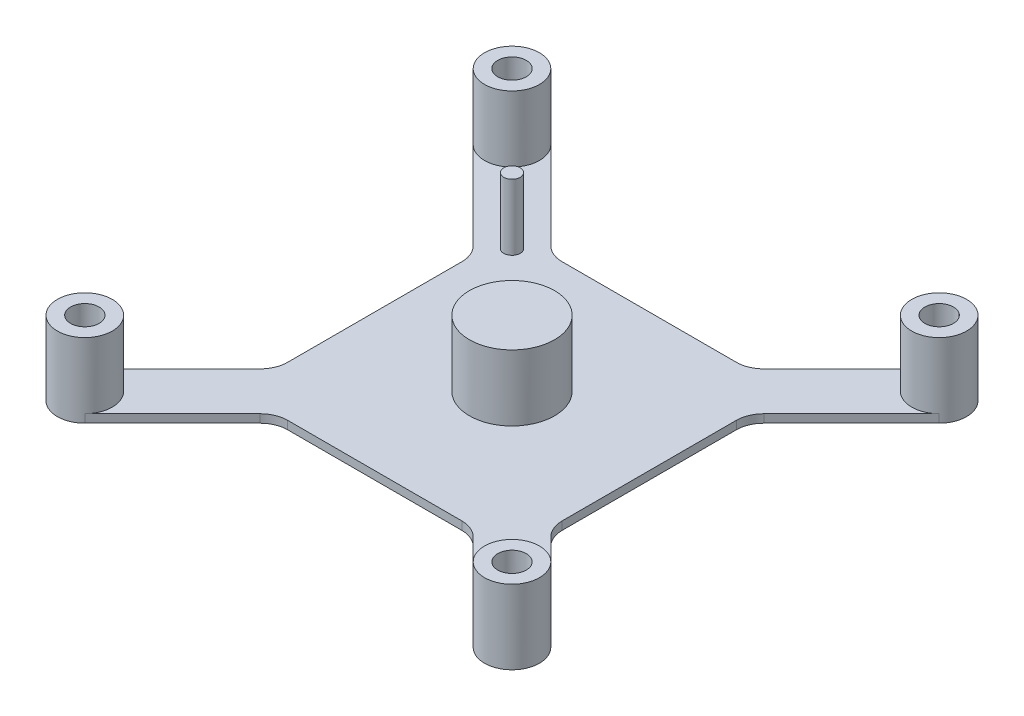
SolidWorks part; units mm, degrees
ref_plane "Front Plane" through (0, 0, 0) normal (0, 0, 1) x (1, 0, 0)
ref_plane "Top Plane" through (0, 0, 0) normal (0, 1, 0) x (1, 0, 0)
ref_plane "Right Plane" through (0, 0, 0) normal (1, 0, 0) x (0, 0, -1)
sketch "Sketch1" plane through (0, 0, 0) normal (0, 1, 0) x (1, 0, 0)
  line L1 (-25, -25) -> (25, -25)
  line L2 (-25, -25) -> (-25, 25)
  line L3 (-25, 25) -> (25, 25)
  line L4 (25, -25) -> (25, 25)
  line L5 (-25, -25) -> (25, 25) construction
  line L6 (-25, 25) -> (25, -25) construction
  circle A0 centre (0, 0) radius 8
  point P0 (0, 0)
  dimension "D2" = 16
  dimension "D1" = 50
extrude "Boss-Extrude1" add sketch "Sketch1" along normal blind 1.5
sketch "Sketch3" plane through (0, 1.5, 0) normal (0, 1, 0) x (1, 0, 0)
  line L0 (0, 0) -> (0, -6.5515) construction
  line L1 (-23, -25) -> (-15, -25)
  line L2 (-25, -23) -> (-25, -15)
  line L3 (-25, -15) -> (-17, -15)
  line L4 (-15, -25) -> (-15, -17)
  line L5 (0, -6.5515) -> (0, 0) construction
  line L6 (0, 0) -> (-7.2066, 0) construction
  line L7 (-25, 15) -> (-17, 15)
  line L8 (-15, 25) -> (-15, 17)
  line L9 (-23, 25) -> (-15, 25)
  line L10 (-25, 23) -> (-25, 15)
  line L11 (25, -15) -> (17, -15)
  line L12 (15, -25) -> (15, -17)
  line L13 (23, -25) -> (15, -25)
  line L14 (25, -23) -> (25, -15)
  line L15 (25, 23) -> (25, 15)
  line L16 (23, 25) -> (15, 25)
  line L17 (15, 25) -> (15, 17)
  line L18 (25, 15) -> (17, 15)
  line L19 (-25, 22.5) -> (-22.5, 22.5) construction
  line L20 (-22.5, 22.5) -> (-22.5, 25) construction
  arc A0 (23, -25) -> (25, -23) centre (23, -23) ccw
  arc A1 (25, 23) -> (23, 25) centre (23, 23) ccw
  arc A2 (-23, 25) -> (-25, 23) centre (-23, 23) ccw
  arc A3 (-23, -25) -> (-25, -23) centre (-23, -23) cw
  arc A4 (17, -15) -> (15, -17) centre (17, -17) ccw
  arc A5 (15, 17) -> (17, 15) centre (17, 17) ccw
  arc A6 (-17, 15) -> (-15, 17) centre (-17, 17) ccw
  arc A7 (-17, -15) -> (-15, -17) centre (-17, -17) cw
  circle A16 centre (-22.5, 22.5) radius 1.5
  circle A17 centre (-17, 17) radius 1.5
  point P23 (25, -25)
  point P26 (25, 25)
  point P29 (-25, 25)
  point P32 (-25, -25)
  point P35 (15, -15)
  point P38 (15, 15)
  point P41 (-15, 15)
  point P44 (-15, -15)
  dimension "D2" = 2
  dimension "D3" = 2.5
  dimension "D4" = 3
  dimension "D6" = 3
  dimension "D1" = 10
  dimension "D5" = 2.5
sketch "Sketch5" plane through (0, 1.5, 0) normal (0, 1, 0) x (1, 0, 0)
  line L0 (0, 0) -> (0, 33.3014) construction
  line L1 (0, 0) -> (36.9203, 0) construction
  line L2 (0, 0) -> (38.8909, 38.8909) construction
  line L3 (0, 0) -> (-38.8909, -38.8909) construction
  line L4 (-35.3553, -42.4264) -> (-42.4264, -35.3553) construction
  line L5 (42.4264, 35.3553) -> (35.3553, 42.4264) construction
  line L6 (-42.4264, -35.3553) -> (-25, -17.9289)
  line L7 (-25, 25) -> (-25, -25) construction
  line L8 (-35.3553, -42.4264) -> (-17.9289, -25)
  line L9 (-25, -25) -> (25, -25) construction
  line L10 (35.3553, 42.4264) -> (17.9289, 25)
  line L11 (25, 25) -> (-25, 25) construction
  line L12 (42.4264, 35.3553) -> (25, 17.9289)
  line L13 (25, -25) -> (25, 25) construction
  line L14 (-42.4264, -35.3553) -> (-45.9619, -38.8909)
  line L15 (-45.9619, -38.8909) -> (-38.8909, -45.9619)
  line L16 (-38.8909, -45.9619) -> (-35.3553, -42.4264)
  line L17 (35.3553, 42.4264) -> (38.8909, 45.9619)
  line L18 (38.8909, 45.9619) -> (45.9619, 38.8909)
  line L19 (45.9619, 38.8909) -> (42.4264, 35.3553)
  line L20 (45.9619, -38.8909) -> (42.4264, -35.3553)
  line L21 (35.3553, -42.4264) -> (38.8909, -45.9619)
  line L22 (38.8909, -45.9619) -> (45.9619, -38.8909)
  line L23 (42.4264, -35.3553) -> (25, -17.9289)
  line L24 (35.3553, -42.4264) -> (17.9289, -25)
  line L25 (-42.4264, 35.3553) -> (-45.9619, 38.8909)
  line L26 (-38.8909, 45.9619) -> (-35.3553, 42.4264)
  line L27 (-45.9619, 38.8909) -> (-38.8909, 45.9619)
  line L28 (-35.3553, 42.4264) -> (-17.9289, 25)
  line L29 (-42.4264, 35.3553) -> (-25, 17.9289)
  line L30 (-25, 17.9289) -> (-25, -17.9289)
  line L31 (-17.9289, -25) -> (17.9289, -25)
  line L32 (25, 17.9289) -> (25, -17.9289)
  line L33 (-17.9289, 25) -> (17.9289, 25)
  circle A0 centre (-38.8909, -38.8909) radius 2.6
  circle A1 centre (38.8909, 38.8909) radius 2.6
  circle A2 centre (38.8909, -38.8909) radius 2.6
  circle A3 centre (-38.8909, 38.8909) radius 2.6
  circle A4 centre (0, 0) radius 8 construction
  circle A5 centre (0, 0) radius 8
  point P9 (-38.8909, -38.8909)
  point P12 (38.8909, 38.8909)
  dimension "D6" = 5.2
  dimension "D1" = 45
  dimension "D2" = 55
  dimension "D3" = 10
  dimension "D4" = 5
  dimension "D5" = 5
extrude "Boss-Extrude3" add sketch "Sketch5" against normal blind 1.5
fillet "Fillet1" radius 5 16 edges at (17.9289, 0.75, 25) (38.8909, 0.75, 45.9619) (45.9619, 0.75, 38.8909) (25, 0.75, 17.9289) (25, 0.75, -17.9289) (45.9619, 0.75, -38.8909) (38.8909, 0.75, -45.9619) (17.9289, 0.75, -25) (-17.9289, 0.75, -25) (-38.8909, 0.75, -45.9619) (-45.9619, 0.75, -38.8909) (-25, 0.75, -17.9289) (-25, 0.75, 17.9289) (-45.9619, 0.75, 38.8909) (-38.8909, 0.75, 45.9619) (-17.9289, 0.75, 25)
sketch "Sketch6" plane through (0, 1.5, 0) normal (0, 1, 0) x (1, 0, 0)
  circle A0 centre (38.8909, -38.8909) radius 2.6 construction
  circle A1 centre (38.8909, 38.8909) radius 2.6 construction
  circle A2 centre (-38.8909, 38.8909) radius 2.6 construction
  circle A3 centre (-38.8909, -38.8909) radius 2.6 construction
  circle A4 centre (38.8909, -38.8909) radius 2.6
  circle A5 centre (38.8909, 38.8909) radius 2.6
  circle A6 centre (-38.8909, 38.8909) radius 2.6
  circle A7 centre (-38.8909, -38.8909) radius 2.6
  circle A8 centre (-38.8909, -38.8909) radius 5
  circle A9 centre (-38.8909, 38.8909) radius 5
  circle A10 centre (38.8909, 38.8909) radius 5
  circle A11 centre (38.8909, -38.8909) radius 5
extrude "Boss-Extrude4" add sketch "Sketch6" along normal blind 12
sketch "Sketch7" plane through (0, 1.5, 0) normal (0, 1, 0) x (1, 0, 0)
  circle A0 centre (0, 0) radius 8.25
  dimension "D1" = 16.5
extrude "Boss-Extrude5" add sketch "Sketch7" against normal blind 1.5
sketch "Sketch8" plane through (0, 1.5, 0) normal (0, 1, 0) x (1, 0, 0)
  circle A0 centre (0, 0) radius 7.75
  dimension "D1" = 15.5
extrude "Boss-Extrude6" add sketch "Sketch8" along normal up to surface (12 mm away) up to face at (-38.8909, 13.5, -33.8909)
sketch "Sketch9" plane through (0, 1.5, 0) normal (0, 1, 0) x (1, 0, 0)
  circle A0 centre (-22.5, 22.5) radius 1.5 construction
  circle A1 centre (-22.5, 22.5) radius 1.5
extrude "Boss-Extrude7" add sketch "Sketch9" along normal up to surface (12 mm away) up to face at (-38.8909, 13.5, -33.8909)
